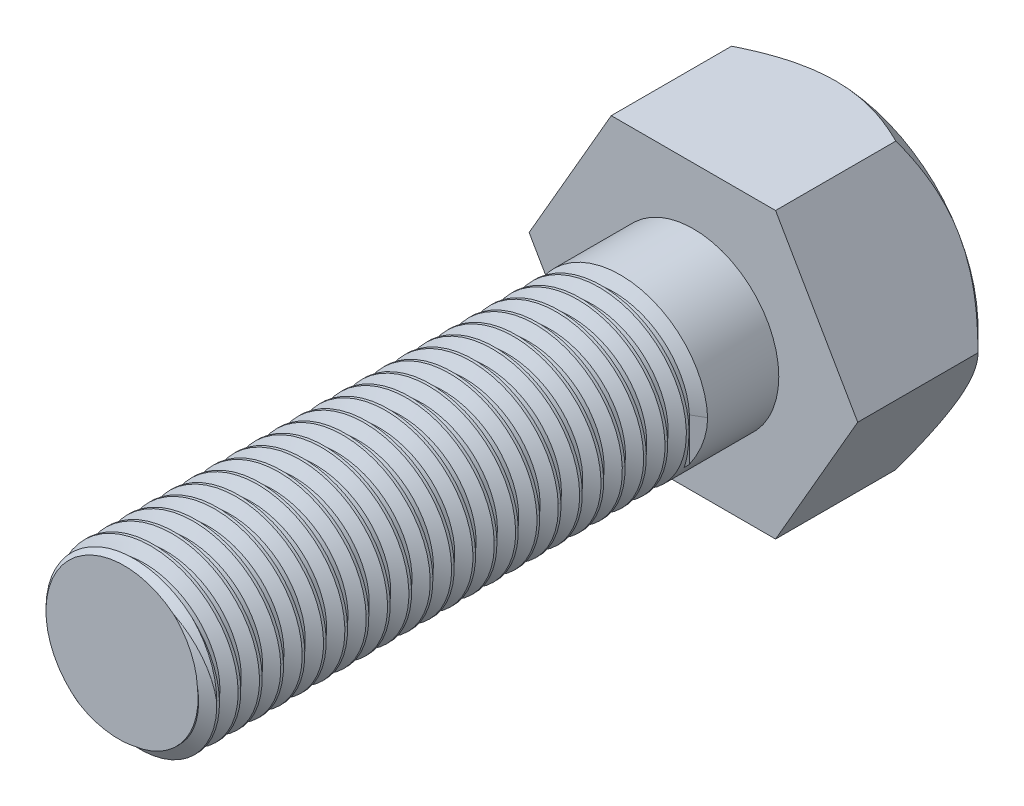
SolidWorks part; units mm, degrees
ref_plane "Front Plane" through (0, 0, 0) normal (0, 0, 1) x (1, 0, 0)
ref_plane "Top Plane" through (0, 0, 0) normal (0, 1, 0) x (1, 0, 0)
ref_plane "Right Plane" through (0, 0, 0) normal (1, 0, 0) x (0, 0, -1)
sketch "Sketch2" plane through (0, 0, 0) normal (0, 0, 1) x (1, 0, 0)
  line L1 (5.7735, 10) -> (-5.7735, 10)
  line L2 (-5.7735, 10) -> (-11.547, 0)
  line L3 (-11.547, 0) -> (-5.7735, -10)
  line L4 (-5.7735, -10) -> (5.7735, -10)
  line L5 (5.7735, -10) -> (11.547, 0)
  line L6 (11.547, 0) -> (5.7735, 10)
  circle A0 centre (0, 0) radius 10 construction
  dimension "D1" = 20
extrude "Boss-Extrude2" add sketch "Sketch2" along normal mid plane 10
sketch "Sketch3" plane through (0, 0, 5) normal (0, 0, 1) x (1, 0, 0)
  circle A0 centre (0, 0) radius 6
  dimension "D1" = 12
extrude "Boss-Extrude3" add sketch "Sketch3" along normal blind 40
chamfer "Chamfer1" distance 0.5 angle 45 1 edges at (6, 0, 45)
sketch "Sketch4" plane through (0, 0, -5) normal (0, 0, -1) x (-1, 0, 0)
  circle A0 centre (0, 0) radius 10
  dimension "D1" = 20
extrude "Cut-Extrude1" cut sketch "Sketch4" against normal through all draft 45 flip side to cut contours A0
thread "Thread1" pitch 1.5 method cut profile "Thread Profile1" start angle 0, offset 5, length 0, pitch 1.5, diameter 12
ref_plane "Plane1" through (6, 0, 10) normal (0, -1, 0) x (1, 0, 0)
sketch "Thread Profile1" plane through (6, 0, 10) normal (0, -1, 0) x (1, 0, 0)
  line L0 (0, 0) -> (0, 1.5) construction
  line L11 (0, 0) -> (0, 1.3125)
  line L12 (0, 1.3125) -> (-0.8119, 0.8437)
  line L13 (-0.8119, 0.8437) -> (-0.8119, 0.4687)
  line L15 (-0.8119, 0.4687) -> (0, 0)
  line L17 (-0.8119, 0.6562) -> (0, 0.6562) construction
  point P2 (0, 0)
  dimension "Pitch" = 1.5
  dimension "Profile_Angle" = 60
  dimension "Profile_Land" = 0.375
  dimension "Profile_Height" = 0.8119
sketch "Sketch7" plane through (0, 0, 0) normal (0, 1, 0) x (1, 0, 0)
  line L4 (6, -10) -> (5.1881, -10.4687)
  line L5 (5.1881, -10.4687) -> (5.1881, -10.8437)
  line L6 (5.1881, -10.8437) -> (6, -11.3125)
  line L7 (6, -11.3125) -> (6, -10)
  line L8 (6, -10) -> (5.1881, -10.4687)
  line L9 (5.1881, -10.4687) -> (5.1881, -10.8437)
  line L10 (5.1881, -10.8437) -> (6, -11.3125)
  line L11 (6, -11.3125) -> (6, -10)
  dimension "D1" = 0
extrude "Cut-Extrude2" cut sketch "Sketch7" against normal through all
